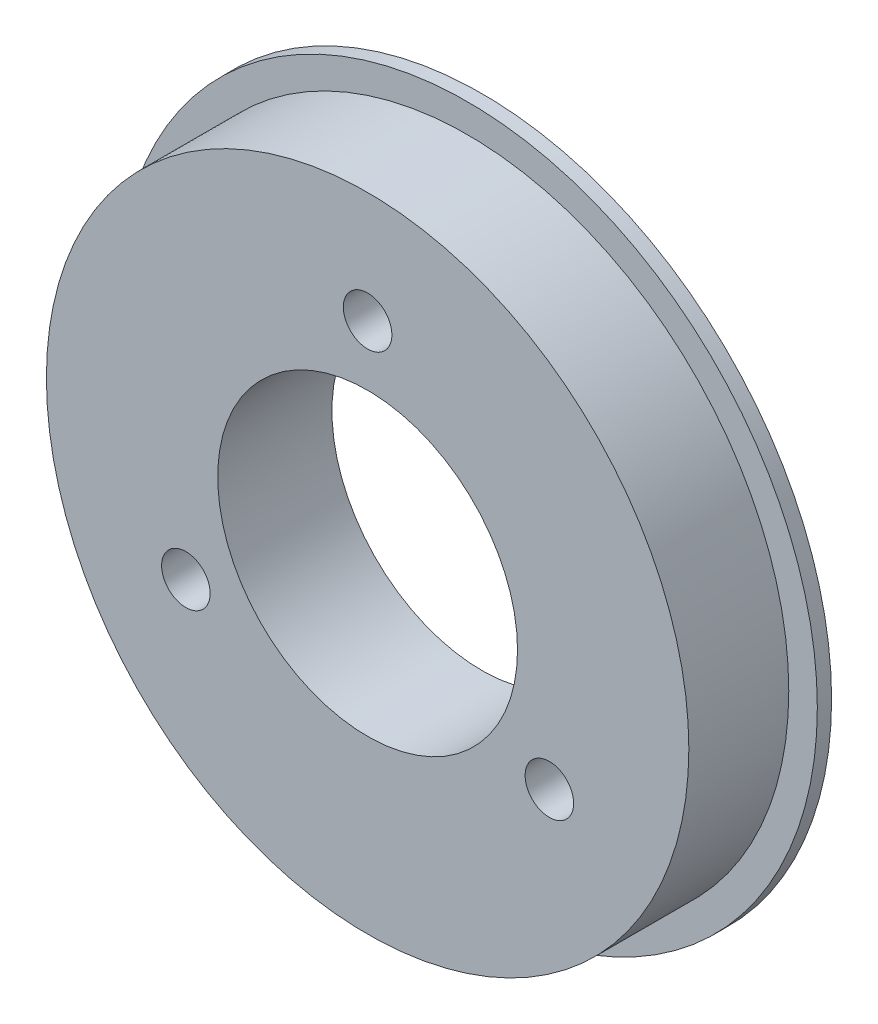
SolidWorks part; units mm, degrees
ref_plane "Front Plane" through (0, 0, 0) normal (0, 0, 1) x (1, 0, 0)
ref_plane "Top Plane" through (0, 0, 0) normal (0, 1, 0) x (1, 0, 0)
ref_plane "Right Plane" through (0, 0, 0) normal (1, 0, 0) x (0, 0, -1)
sketch "Sketch1" plane through (0, 0, 0) normal (0, 0, 1) x (1, 0, 0)
  line L0 (0, 0) -> (0, 14.7) construction
  circle A2 centre (0, 0) radius 22.5
  circle A3 centre (0, 0) radius 10.5
  circle A4 centre (0, 14.7) radius 1.7
  circle A5 centre (0, 0) radius 14.7 construction
  circle A6 centre (12.7306, -7.35) radius 1.7
  circle A7 centre (-12.7306, -7.35) radius 1.7
  circle A9 centre (0, 0) radius 24.5
  dimension "D1" = 45
  dimension "D2" = 21
  dimension "D3" = 3.4
  dimension "D4" = 29.4
  dimension "D6" = 2
  dimension "D5" = 3
extrude "Boss-Extrude2" add sketch "Sketch1" along normal blind 7 contours A2 A7 A6 A4 A3 region at (-21.8636, 0, 0)
extrude "Boss-Extrude3" add sketch "Sketch1<3>" against normal blind 1 contours A9 A2 | A2 A7 A6 A4 A3 region at (-21.8636, 0, 0) region at (-23.807, 0, 0)
sketch "Sketch1<3>" plane through (0, 0, 0) normal (0, 0, 1) x (1, 0, 0) same geometry as "Sketch1"
